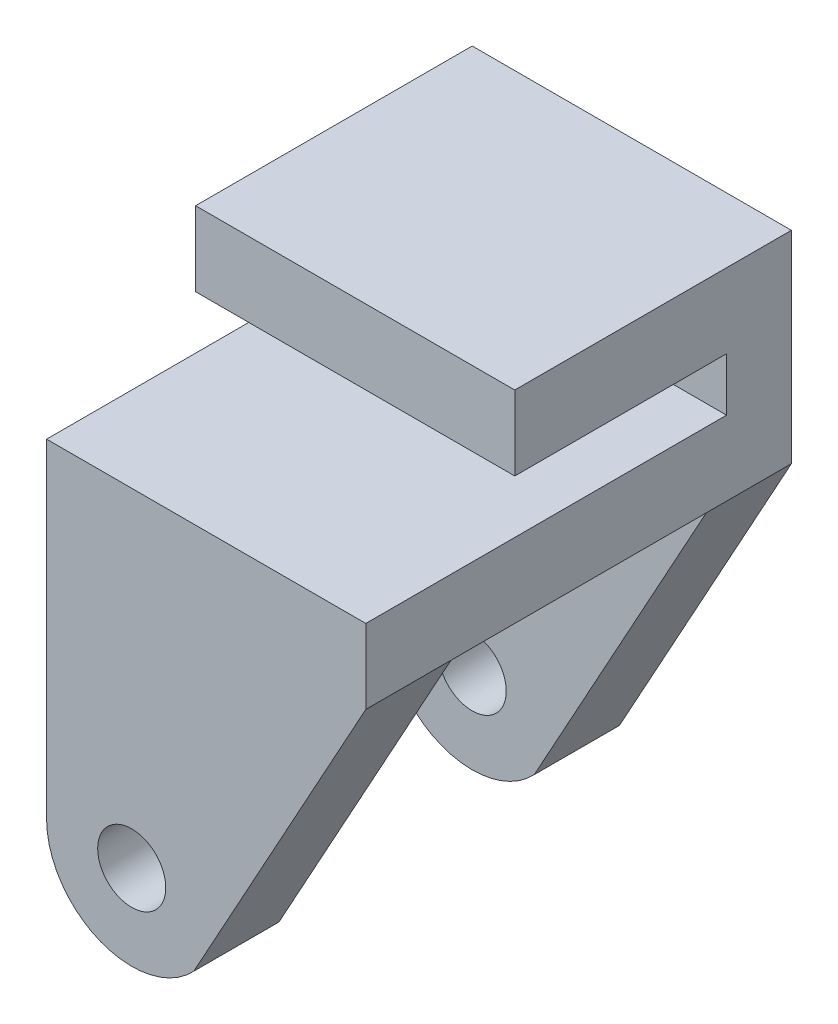
SolidWorks part; units mm, degrees
ref_plane "Front Plane" through (0, 0, 0) normal (0, 0, 1) x (1, 0, 0)
ref_plane "Top Plane" through (0, 0, 0) normal (0, 1, 0) x (1, 0, 0)
ref_plane "Right Plane" through (0, 0, 0) normal (1, 0, 0) x (0, 0, -1)
sketch "Sketch1" plane through (0, 0, 0) normal (1, 0, 0) x (0, 0, -1)
  line L1 (0, 0) -> (20, 0)
  line L2 (0, 0) -> (0, 9.5)
  line L3 (0, 9.5) -> (20, 9.5)
  line L4 (20, 0) -> (20, 9.5)
  dimension "D1" = 9.5
  dimension "D2" = 20
extrude "Boss-Extrude1" add sketch "Sketch1" along normal blind 15 contours L3 L4 L1 L2
sketch "Sketch2" plane through (15, 0, 0) normal (1, 0, 0) x (0, 0, -1)
  line L0 (20, 0) -> (20, 9.5) construction
  line L1 (20, 3.5) -> (3.0475, 3.5)
  line L2 (20, 3.5) -> (20, 6.3375)
  line L3 (13, 6) -> (3.0475, 6)
  line L4 (3.0475, 3.5) -> (3.0475, 6)
  line L6 (0, 9.5) -> (20, 9.5) construction
  line L9 (13, 6) -> (13, 9.5)
  line L10 (13, 9.5) -> (20, 9.5)
  line L11 (20, 6.3375) -> (20, 9.5)
  dimension "D1" = 2.5
  dimension "D2" = 3.5
  dimension "D3" = 7
extrude "Cut-Extrude1" cut sketch "Sketch2" against normal through all and the other way through all
sketch "Sketch4" plane through (0, 0, 0) normal (0, 0, 1) x (1, 0, 0)
  line L0 (0, 0) -> (0, -12)
  line L4 (15, 0) -> (6.9177, -14.6941)
  line L5 (0, 0) -> (15, 0)
  circle A1 centre (3.9998, -11.9581) radius 1.6
  arc A2 (0, -12) -> (6.9177, -14.6941) centre (3.9998, -11.9581) ccw
  dimension "D3" = 3.2
  dimension "D4" = 12
  dimension "D1" = 4
extrude "Boss-Extrude3" add sketch "Sketch4" against normal blind 4
ref_plane "Plane1" through (0, 0, -10) normal (0, 0, 1) x (1, 0, 0)
mirror "Mirror1" about plane through (0, 0, -10) normal (0, 0, 1) of "Boss-Extrude3"
mirror "Mirror2" about plane through (15, 0, -20) normal (0, 0, 1) of "Mirror1", "Boss-Extrude3", "Cut-Extrude1", "Boss-Extrude1"
ref_plane "Plane2" through (0, 0, -20) normal (0, 0, 1) x (1, 0, 0)
sketch "Sketch5" plane through (0, 0, -20) normal (0, 0, 1) x (1, 0, 0)
  line L1 (-0.3001, -17.8504) -> (15.2625, -17.8504)
  line L2 (-0.3001, -17.8504) -> (-0.3001, 9.8665)
  line L3 (-0.3001, 9.8665) -> (15.2625, 9.8665)
  line L4 (15.2625, -17.8504) -> (15.2625, 9.8665)
extrude "Cut-Extrude2" cut sketch "Sketch5" along normal through all
